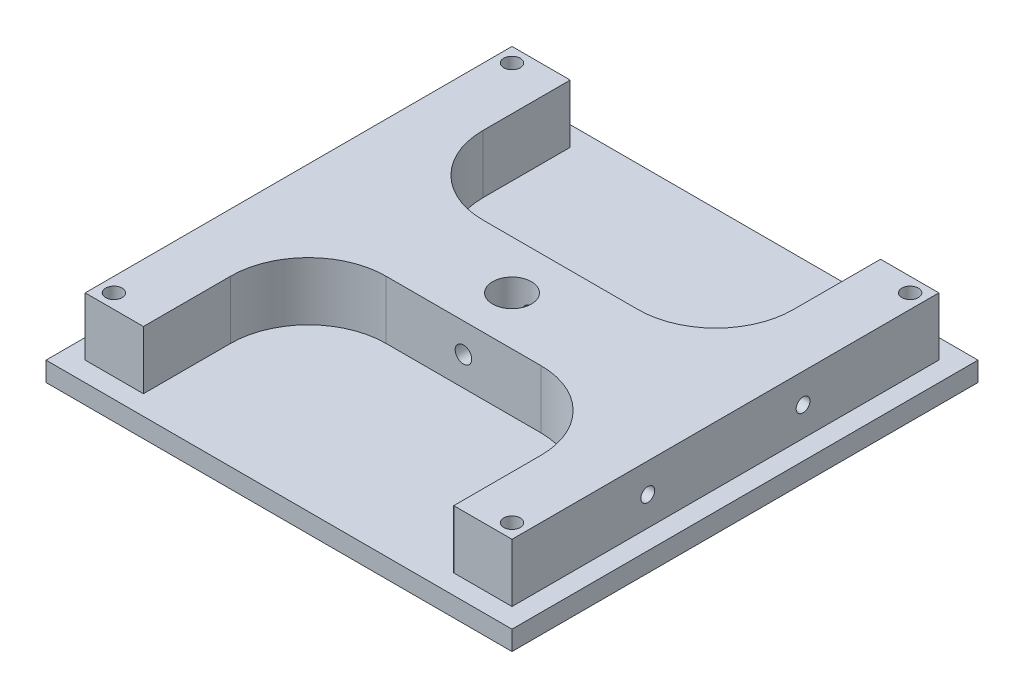
SolidWorks part; units mm, degrees
material "6061-T6 (SS)"
ref_plane "Front Plane" through (0, 0, 0) normal (0, 0, 1) x (1, 0, 0)
ref_plane "Top Plane" through (0, 0, 0) normal (0, 1, 0) x (1, 0, 0)
ref_plane "Right Plane" through (0, 0, 0) normal (1, 0, 0) x (0, 0, -1)
sketch "Sketch1" plane through (0, 0, 0) normal (0, 1, 0) x (1, 0, 0)
  line L1 (-38.1, -38.1) -> (38.1, -38.1)
  line L2 (-38.1, -38.1) -> (-38.1, 38.1)
  line L3 (-38.1, 38.1) -> (38.1, 38.1)
  line L4 (38.1, -38.1) -> (38.1, 38.1)
  line L5 (-38.1, -38.1) -> (38.1, 38.1) construction
  line L6 (-38.1, 38.1) -> (38.1, -38.1) construction
  point P0 (0, 0)
  dimension "D1" = 76.2
  dimension "D2" = 76.2
extrude "Boss-Extrude1" add sketch "Sketch1" along normal blind 3.175
sketch "Sketch2" plane through (0, 3.175, 0) normal (0, 1, 0) x (1, 0, 0)
  line L0 (-38.1, 38.1) -> (-38.1, -38.1) construction
  line L1 (34.8971, -34.8971) -> (-34.8971, -34.8971)
  line L2 (34.8971, -34.8971) -> (34.8971, 34.8971)
  line L3 (34.8971, 34.8971) -> (-34.8971, 34.8971)
  line L4 (-34.8971, -34.8971) -> (-34.8971, 34.8971)
  line L5 (38.1, -38.1) -> (38.1, 38.1) construction
  line L6 (-38.1, -38.1) -> (38.1, -38.1) construction
  line L14 (38.1, 38.1) -> (-38.1, 38.1) construction
  point P0 (0, 0)
  point P6 (0, 0)
  dimension "D1" = 3.2029
  dimension "D2" = 3.2029
  dimension "D3" = 3.2029
  dimension "D4" = 3.2029
extrude "Boss-Extrude2" add sketch "Sketch2" along normal blind 9.525
sketch "Sketch8" plane through (34.8971, 0, 0) normal (1, 0, 0) x (0, 0, -1)
  line L0 (-38.1, 3.175) -> (38.1, 3.175) construction
  point P0 (-12.7, 7.9375)
  dimension "D1" = 4.7625
  dimension "D2" = 12.7
hole_wizard "#4-40 Tapped Hole1" positions "Sketch10" profile "Sketch9" tap size "#4-40" standard "ANSI Inch"
sketch "Sketch10" plane through (34.8971, 0, 0) normal (1, 0, 0) x (0, 0, -1)
  point P0 (-12.7, 7.9375)
sketch "Sketch9" plane through (34.8971, 7.9375, 12.7) normal (0, 1, 0) x (0, 0, -1)
  line L0 (0, 0) -> (0, 7.2832)
  line L1 (0, 7.2832) -> (1.1303, 6.604)
  line L2 (1.1303, 6.604) -> (1.1303, 0)
  line L5 (1.1303, 0) -> (0, 0)
  line L10 (0, 7.2832) -> (-1.1303, 6.604) construction
  line L11 (0, -6.35) -> (0, 107.95) construction
  dimension "Tap Drill Dia." = 2.2606
  dimension "Tap Drill Depth" = 6.604
  dimension "Drill Angle" = 118
cosmetic thread "Hole Thread1" parameters "D1"=2.4486, "D2"=2.8448
mirror "Mirror1" about plane through (0, 0, 0) normal (0, 0, 1) of "#4-40 Tapped Hole1"
mirror "Mirror2" about plane through (0, 0, 0) normal (1, 0, 0) of "Mirror1"
sketch "Sketch11" plane through (0, 0, 0) normal (0, -1, 0) x (1, 0, 0)
  circle A0 centre (32.5501, -32.5501) radius 2.032
  dimension "D1" = 4.064
hole_wizard "#6-32 Tapped Hole1" positions "Sketch13" profile "Sketch12" tap size "#6-32" standard "ANSI Inch" end condition through all
sketch "Sketch13" plane through (0, 0, 0) normal (0, -1, 0) x (-1, 0, 0)
  point P0 (-32.5501, 32.5501)
sketch "Sketch12" plane through (32.5501, 0, -32.5501) normal (1, 0, 0) x (0, 0, -1)
  line L0 (0, 0) -> (0, 12.7)
  line L1 (0, 12.7) -> (1.3525, 12.7)
  line L2 (1.3525, 12.7) -> (1.3525, 0)
  line L5 (1.3525, 0) -> (0, 0)
  line L11 (0, -6.35) -> (0, 107.95) construction
  dimension "Thru Tap Drill Dia." = 2.7051
  dimension "Thru Tap Drill Depth" = 12.7
cosmetic thread "Hole Thread2" parameters "D2"=3.5052
ref_axis "Axis1" through (0, -0.635, 0) along (0, 1, 0)
pattern_circular "CirPattern1" count 4 over 360 about axis through (0, -0.635, 0) along (0, 1, 0) of "#6-32 Tapped Hole1"
sketch "Sketch14" plane through (0, 0, 0) normal (0, -1, 0) x (1, 0, 0)
  circle A0 centre (0, 0) radius 3.175
  dimension "D1" = 6.35
extrude "Cut-Extrude1" cut sketch "Sketch14" against normal through all
sketch "Sketch15" plane through (0, 12.7, 0) normal (0, 1, 0) x (1, 0, 0)
  line L0 (-25.3721, -7.9375) -> (25.3721, -7.9375)
  line L1 (25.3721, -7.9375) -> (25.3721, -34.8971)
  line L2 (-34.8971, -34.8971) -> (34.8971, -34.8971) construction
  line L3 (-25.3721, -7.9375) -> (-25.3721, -34.8971)
  line L4 (-34.8971, 34.8971) -> (-34.8971, -34.8971) construction
  line L5 (34.8971, -34.8971) -> (34.8971, 34.8971) construction
  line L6 (-25.3721, -34.8971) -> (25.3721, -34.8971)
  dimension "D1" = 9.525
  dimension "D2" = 9.525
  dimension "D3" = 7.9375
extrude "Cut-Extrude2" cut sketch "Sketch15" against normal blind 9.525
fillet "Fillet1" radius 12.7 2 edges at (25.3721, 7.9375, 7.9375) (-25.3721, 7.9375, 7.9375)
sketch "Sketch16" plane through (0, 0, 7.9375) normal (0, 0, 1) x (1, 0, 0)
  line L0 (12.6721, 3.175) -> (-12.6721, 3.175) construction
  point P0 (0, 7.9375)
  dimension "D1" = 4.7625
hole_wizard "#6-32 Tapped Hole2" positions "Sketch18" profile "Sketch17" tap size "#6-32" standard "ANSI Inch"
sketch "Sketch18" plane through (0, 0, 7.9375) normal (0, 0, 1) x (1, 0, 0)
  point P0 (0, 7.9375)
sketch "Sketch17" plane through (0, 7.9375, 7.9375) normal (1, 0, 0) x (0, -1, 0)
  line L0 (0, 0) -> (0, 10.4647)
  line L1 (0, 10.4647) -> (1.3525, 9.652)
  line L2 (1.3525, 9.652) -> (1.3525, 0)
  line L5 (1.3525, 0) -> (0, 0)
  line L10 (0, 10.4647) -> (-1.3526, 9.652) construction
  line L11 (0, -6.35) -> (0, 107.95) construction
  dimension "Tap Drill Dia." = 2.7051
  dimension "Tap Drill Depth" = 9.652
  dimension "Drill Angle" = 118
cosmetic thread "Hole Thread3" parameters "D1"=6.35, "D2"=3.5052
mirror "Mirror3" about plane through (0, 0, 0) normal (0, 0, 1) of "Fillet1", "Cut-Extrude2", "#6-32 Tapped Hole2"
equation "\"D2@Sketch2\"=\"D1@Sketch2\""
equation "\"D2@Sketch1\"=\"D1@Sketch1\""
equation "\"D3@Sketch2\"=\"D2@Sketch2\""
equation "\"D4@Sketch2\"=\"D2@Sketch2\""
equation "\"D2@Sketch15\"=\"D1@Sketch15\""
